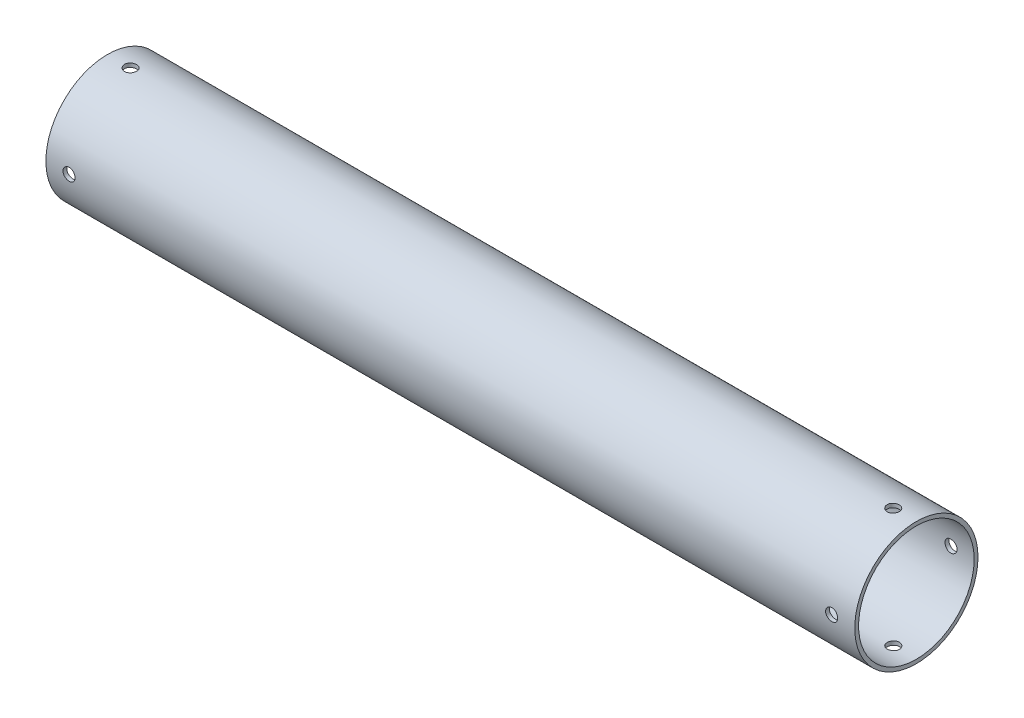
SolidWorks part; units mm, degrees
other "Exploded View1" [suppressed]
material "PC High Viscosity"
ref_plane "Front Plane" through (0, 0, 0) normal (0, 0, 1) x (1, 0, 0)
ref_plane "Top Plane" through (0, 0, 0) normal (0, 1, 0) x (1, 0, 0)
ref_plane "Right Plane" through (0, 0, 0) normal (1, 0, 0) x (0, 0, -1)
sketch "Sketch1" plane through (0, 0, 0) normal (1, 0, 0) x (0, 0, -1)
  circle A0 centre (0, 0) radius 25.4
  dimension "D1" = 50.8
extrude "Extrude-Thin1" add sketch "Sketch1" along normal mid plane 333.375 thin thin type one direction reverse wall 1.5875
sketch "Sketch2" plane through (0, 0, 0) normal (0, 0, 1) x (1, 0, 0)
  line L0 (-166.6875, -25.4) -> (166.6875, -25.4) construction
  line L1 (111.4135, -25.4) -> (132.4135, -25.4)
  line L2 (111.4135, -25.4) -> (111.4135, 25.4)
  line L3 (111.4135, 25.4) -> (132.4135, 25.4)
  line L4 (132.4135, -25.4) -> (132.4135, 25.4)
  line L5 (166.6875, 25.4) -> (-166.6875, 25.4) construction
  line L6 (166.6875, -25.4) -> (166.6875, 25.4) construction
  line L7 (0, 0) -> (0, 11.1276) construction
  line L8 (-132.4135, -25.4) -> (-132.4135, 25.4)
  line L9 (-111.4135, 25.4) -> (-132.4135, 25.4)
  line L10 (-111.4135, -25.4) -> (-111.4135, 25.4)
  line L11 (-111.4135, -25.4) -> (-132.4135, -25.4)
  dimension "D1" = 34.274
  dimension "D2" = 21
sketch "Sketch3" plane through (0, 0, 0) normal (0, 0, 1) x (1, 0, 0)
  line L0 (-166.6875, 25.4) -> (-166.6875, -25.4) construction
  line L1 (166.6875, -25.4) -> (166.6875, 25.4) construction
  circle A0 centre (-157.1625, 0) radius 2.4892
  circle A1 centre (157.1625, 0) radius 2.4892
  dimension "D1" = 4.9784
  dimension "D2" = 9.525
  dimension "D3" = 9.525
extrude "Cut-Extrude1" cut sketch "Sketch3" against normal through all both and the other way through all
sketch "Sketch4" plane through (0, 0, 0) normal (0, 1, 0) x (1, 0, 0)
  line L0 (-166.6875, 25.4) -> (-166.6875, -25.4) construction
  line L1 (166.6875, -23.8125) -> (166.6875, 23.8125) construction
  circle A0 centre (-157.1625, 0) radius 2.4892
  circle A1 centre (157.1625, 0) radius 2.4892
  point P4 (0, 0)
  dimension "D1" = 4.9784
  dimension "D2" = 9.525
  dimension "D3" = 9.525
extrude "Cut-Extrude2" cut sketch "Sketch4" against normal through all both and the other way through all
equation "\"D2@Sketch2\"=21mm"
